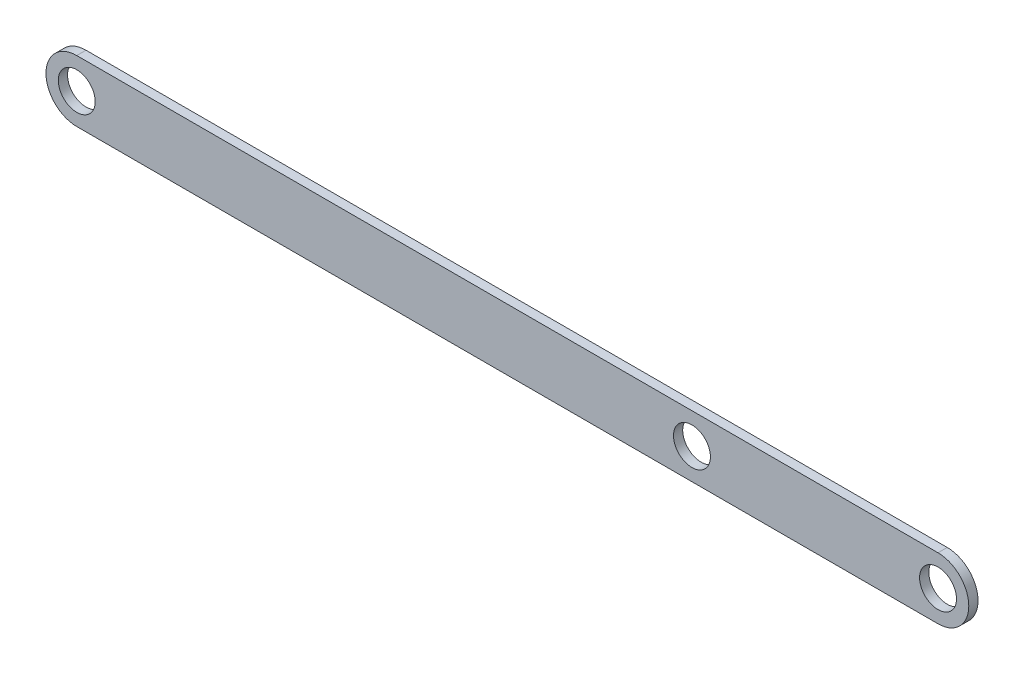
SolidWorks part; units mm, degrees
ref_plane "Front Plane" through (0, 0, 0) normal (0, 0, 1) x (1, 0, 0)
ref_plane "Top Plane" through (0, 0, 0) normal (0, 1, 0) x (1, 0, 0)
ref_plane "Right Plane" through (0, 0, 0) normal (1, 0, 0) x (0, 0, -1)
sketch "Sketch1" plane through (0, 0, 0) normal (0, 0, 1) x (1, 0, 0)
  line L0 (0, 5) -> (140, 5)
  line L6 (0, -5) -> (140, -5)
  arc A2 (0, 5) -> (0, -5) centre (0, 0) ccw
  arc A3 (140, -5) -> (140, 5) centre (140, 0) ccw
  dimension "D1" = 10
  dimension "D2" = 140
extrude "Boss-Extrude1" add sketch "Sketch1" along normal blind 1.5
sketch "Sketch2" plane through (0, 0, 1.5) normal (0, 0, 1) x (1, 0, 0)
  circle A0 centre (0, 0) radius 3
  circle A2 centre (140, 0) radius 3
  circle A3 centre (100, 0) radius 3
  point P5 (0, 0)
  dimension "D1" = 6
  dimension "D2" = 140
  dimension "D3" = 40
extrude "Cut-Extrude1" cut sketch "Sketch2" against normal through all
